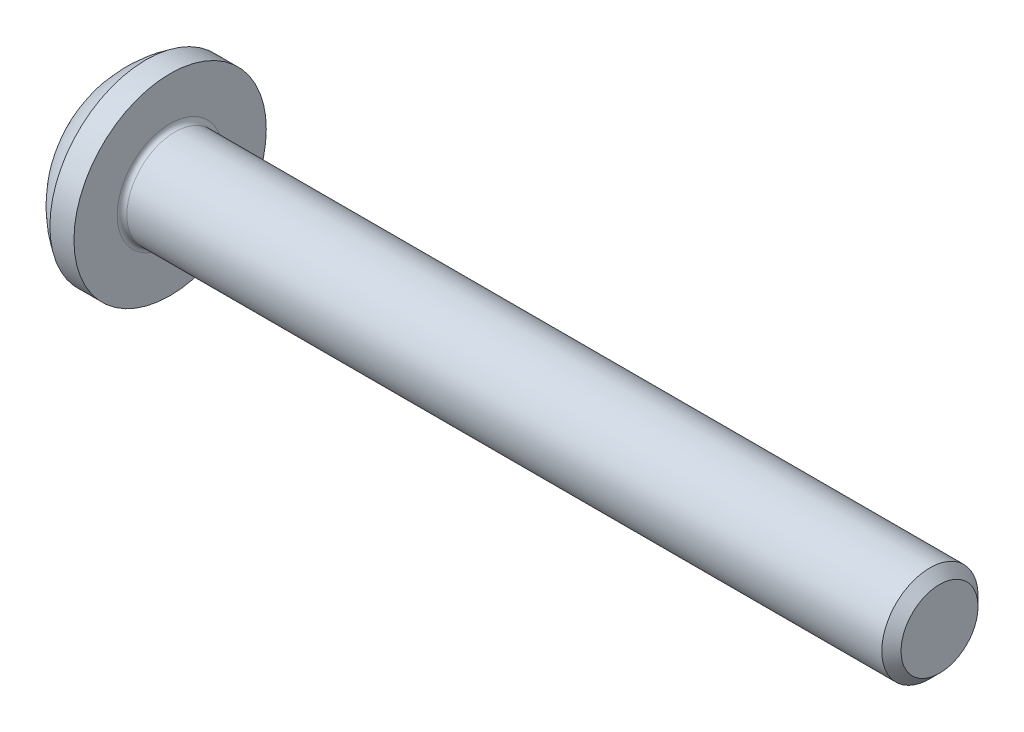
SolidWorks part; units mm, degrees
ref_plane "前视基准面" through (0, 0, 0) normal (0, 0, 1) x (1, 0, 0)
ref_plane "上视基准面" through (0, 0, 0) normal (0, 1, 0) x (1, 0, 0)
ref_plane "右视基准面" through (0, 0, 0) normal (1, 0, 0) x (0, 0, -1)
sketch "草图2" plane through (0, 0, 0) normal (0, 0, 1) x (1, 0, 0)
  line L0 (-1.3318, 0) -> (6.5885, 0) construction
  line L1 (0, 0) -> (17.6, 0)
  line L2 (17.6, 0) -> (17.6, 1)
  line L3 (17.6, 1) -> (1.7, 1)
  line L6 (1.6, 1.1) -> (1.6, 2)
  line L7 (1.6, 2) -> (1.1, 2)
  arc A0 (1.7, 1) -> (1.6, 1.1) centre (1.7, 1.1) cw
  arc A1 (0, 0) -> (1.1, 2) centre (2.3682, 0) cw
  dimension "D3" = 0.5
  dimension "D1" = 0.1
  dimension "d" = 2
  dimension "l" = 16
  dimension "D2" = 2
  dimension "k" = 1.6
revolve "基体-旋转" add sketch "草图2" angle 360 about L0
cosmetic thread "装饰螺纹线1" [suppressed] parameters "D1"=9, "D2"=2.598
sketch "草图5" plane through (0, 0, 0) normal (1, 0, 0) x (0, 0, -1)
  line L1 (0.25, 0.95) -> (-0.25, 0.95)
  line L2 (0.25, 0.95) -> (0.25, -0.95)
  line L3 (0.25, -0.95) -> (-0.25, -0.95)
  line L4 (-0.25, 0.95) -> (-0.25, -0.95)
  point P4 (0.25, 0)
  point P5 (0, 0.95)
  dimension "D1" = 0.5
  dimension "m" = 1.9
ref_plane "基准面12" through (1.2, 0, 0) normal (1, 0, 0) x (0, 0, -1)
sketch "草图6" plane through (1.2, 0, 0) normal (1, 0, 0) x (0, 0, -1)
  point P0 (0, 0)
loft "切除-放样1" cut profiles "草图6", "草图5"
ref_plane "基准面2" through (0, 0, 0) normal (0, -0.7071, 0.7071) x (1, 0, 0)
mirror "镜向1" about plane through (0, 0, 0) normal (0, -0.7071, 0.7071) of "切除-放样1"
ref_axis "基准轴1" through (17.6, 0, 0) along (-1, 0, 0)
ref_plane "基准面3" through (1.6, 0, 0) normal (1, 0, 0) x (0, 0, -1)
chamfer "倒角1" distance 0.2 angle 45 1 edges at (17.6, 0, 1)
ref_plane "基准面1" through (1.6, 0, 0) normal (1, 0, 0) x (0, 0, -1)
